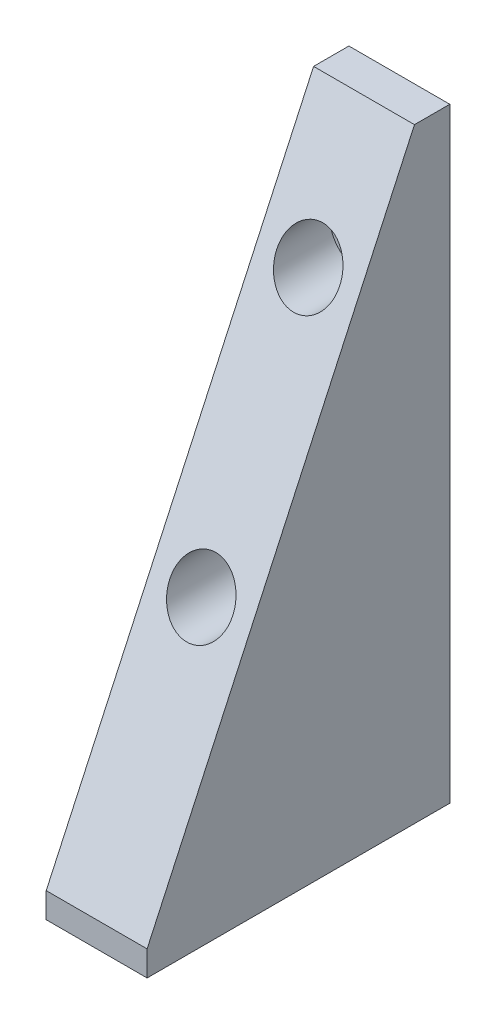
SolidWorks part; units mm, degrees
ref_plane "Front Plane" through (0, 0, 0) normal (0, 0, 1) x (1, 0, 0)
ref_plane "Top Plane" through (0, 0, 0) normal (0, 1, 0) x (1, 0, 0)
ref_plane "Right Plane" through (0, 0, 0) normal (1, 0, 0) x (0, 0, -1)
sketch "Sketch1" plane through (0, 0, 0) normal (1, 0, 0) x (0, 0, -1)
  line L0 (21.526, 126.619) -> (-45.784, -19.431)
  line L1 (-45.784, -25.781) -> (30.416, -25.781)
  line L2 (30.416, -25.781) -> (30.416, 126.619)
  line L3 (30.416, 88.4519) -> (3.9359, 88.4519) construction
  line L4 (21.526, 126.619) -> (30.416, 126.619)
  line L5 (-45.784, -19.431) -> (-45.784, -25.781)
  line L6 (30.416, 59.5647) -> (-9.3773, 59.5647) construction
  dimension "D1" = 76.2
  dimension "D2" = 152.4
  dimension "D3" = 8.89
  dimension "D4" = 6.35
extrude "Boss-Extrude2" add sketch "Sketch1" along normal blind 25.4
sketch "Sketch2" plane through (0, 0, 0) normal (-1, 0, 0) x (0, 0, 1)
  line L0 (-30.416, 96.139) -> (-11.366, 96.139) construction
  line L2 (-30.416, -25.781) -> (-30.416, 126.619) construction
  line L3 (-30.416, 37.719) -> (-10.096, 37.719) construction
  line L4 (-30.416, 126.619) -> (-21.526, 126.619) construction
  point P8 (-25.971, 126.619)
  dimension "D1" = 30.48
  dimension "D2" = 88.9
  dimension "D3" = 19.05
  dimension "D4" = 20.32
ref_plane "Plane1" through (0, 96.139, -11.366) normal (0, 0, 1) x (1, 0, 0)
ref_plane "Plane2" through (0, 37.719, -10.096) normal (0, 0, 1) x (1, 0, 0)
hole_wizard "CBORE for 3/8 Socket Head Cap Screw1" positions "Sketch3" profile "Sketch4" counterbore size "3/8" standard "ANSI Inch" end condition through all
sketch "Sketch3" plane through (0, 96.139, -11.366) normal (0, 0, 1) x (1, 0, 0)
  line L0 (0, 30.48) -> (0, -115.57) construction
  line L1 (25.4, 30.48) -> (0, 30.48) construction
  point P0 (12.7, 0)
  point P8 (12.7, 30.48)
  dimension "D1" = 12.7
  dimension "D2" = 30.48
sketch "Sketch4" plane through (12.7, 96.139, -11.366) normal (1, 0, 0) x (0, -1, 0)
  line L0 (0, 0) -> (0, 19.05)
  line L1 (0, 19.05) -> (4.9022, 19.05)
  line L3 (4.9022, 19.05) -> (4.9022, 9.525)
  line L4 (4.9022, 9.525) -> (7.9375, 9.525)
  line L5 (7.9375, 9.525) -> (7.9375, 0)
  line L7 (7.9375, 0) -> (0, 0)
  line L11 (0, -6.35) -> (0, 107.95) construction
  dimension "Thru Hole Dia." = 9.8044
  dimension "Thru Hole Depth" = 19.05
  dimension "C'Bore Dia." = 15.875
  dimension "C'Bore Depth" = 9.525
hole_wizard "CBORE for 3/8 Socket Head Cap Screw2" positions "Sketch5" profile "Sketch6" counterbore size "3/8" standard "ANSI Inch" end condition through all
sketch "Sketch5" plane through (0, 37.719, -10.096) normal (0, 0, 1) x (1, 0, 0)
  line L0 (0, -63.5) -> (0, 88.9) construction
  line L3 (25.4, 88.9) -> (0, 88.9) construction
  point P0 (12.7, 0)
  point P13 (12.7, 88.9)
  dimension "D1" = 12.7
  dimension "D2" = 88.9
sketch "Sketch6" plane through (12.7, 37.719, -10.096) normal (1, 0, 0) x (0, -1, 0)
  line L0 (0, 0) -> (0, 20.32)
  line L1 (0, 20.32) -> (4.9022, 20.32)
  line L3 (4.9022, 20.32) -> (4.9022, 9.525)
  line L4 (4.9022, 9.525) -> (7.9375, 9.525)
  line L5 (7.9375, 9.525) -> (7.9375, 0)
  line L7 (7.9375, 0) -> (0, 0)
  line L11 (0, -6.35) -> (0, 107.95) construction
  dimension "Thru Hole Dia." = 9.8044
  dimension "Thru Hole Depth" = 20.32
  dimension "C'Bore Dia." = 15.875
  dimension "C'Bore Depth" = 9.525
sketch "Sketch7" plane through (0, 96.139, -11.366) normal (0, 0, 1) x (1, 0, 0)
  circle A0 centre (12.7, -58.42) radius 7.9375 construction
  circle A1 centre (12.7, 0) radius 7.9375 construction
  circle A2 centre (12.7, -58.42) radius 7.9375
  circle A3 centre (12.7, 0) radius 7.9375
extrude "Cut-Extrude2" cut sketch "Sketch7" along normal up to next
hole_wizard "3/8-16 Tapped Hole1" positions "3DSketch4" profile "Sketch9" tap size "3/8-16" standard "ANSI Inch"
sketch3d "3DSketch4"
  line L0 (25.4, -25.781, -30.416) -> (0, -25.781, -30.416) construction
  line L2 (0, -25.781, 45.784) -> (0, -25.781, -30.416) construction
  point P0 (12.7, -25.781, -15.176)
  point P2 (12.7, -25.781, 25.464)
  dimension "D1" = 15.24
  dimension "D2" = 40.64
  dimension "D3" = 12.7
  dimension "D4" = 12.7
sketch "Sketch9" plane through (12.7, -25.781, -15.176) normal (1, 0, 0) x (0, 0, -1)
  line L0 (0, 0) -> (0, 27.7847)
  line L1 (0, 27.7847) -> (3.9687, 25.4)
  line L2 (3.9687, 25.4) -> (3.9687, 0)
  line L5 (3.9687, 0) -> (0, 0)
  line L10 (0, 27.7847) -> (-3.9688, 25.4) construction
  line L11 (0, -6.35) -> (0, 107.95) construction
  dimension "Tap Drill Dia." = 7.9375
  dimension "Tap Drill Depth" = 25.4
  dimension "Drill Angle" = 118
cosmetic thread "Hole Thread1" parameters "D1"=20.32, "D2"=9.525
cosmetic thread "Hole Thread2" parameters "D1"=20.32, "D2"=9.525
